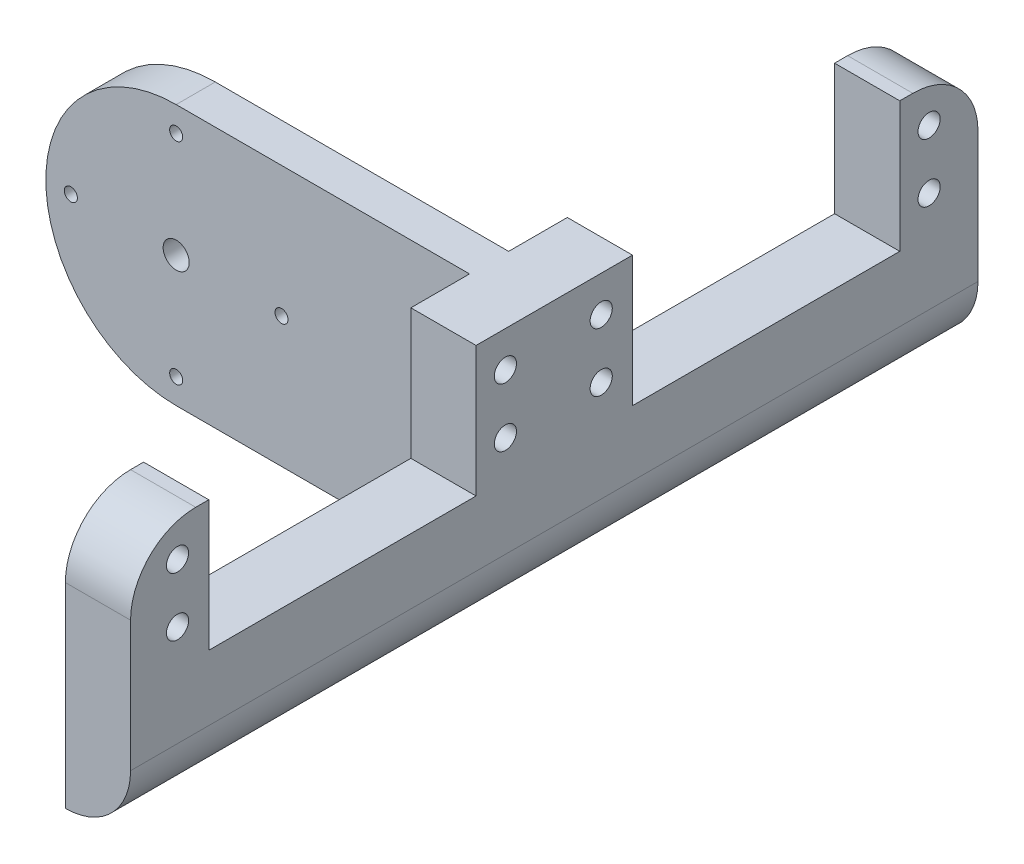
SolidWorks part; units mm, degrees
ref_plane "Front" through (0, 0, 0) normal (0, 0, 1) x (1, 0, 0)
ref_plane "Top" through (0, 0, 0) normal (0, 1, 0) x (1, 0, 0)
ref_plane "Right" through (0, 0, 0) normal (1, 0, 0) x (0, 0, -1)
sketch "스케치1" plane through (0, 0, 0) normal (0, 0, 1) x (1, 0, 0)
  line L0 (0, 20) -> (45, 20)
  line L1 (0, -20) -> (45, -20)
  line L2 (45, 20) -> (45, -20)
  line L3 (0, 16.16) -> (0, 0) construction
  circle A0 centre (0, 0) radius 2
  arc A1 (0, 20) -> (0, -20) centre (0, 0) ccw
  circle A2 centre (0, 16.16) radius 1
  circle A3 centre (16.16, 0) radius 1
  circle A4 centre (0, -16.16) radius 1
  circle A5 centre (-16.16, 0) radius 1
  point P18 (0, 0)
  dimension "D1" = 20
  dimension "D2" = 4
  dimension "D3" = 2
  dimension "D4" = 16.16
  dimension "D5" = 45
extrude "보스-돌출1" add sketch "스케치1" along normal blind 3 and the other way blind 3
sketch "스케치2" plane through (45, 0, 0) normal (1, 0, 0) x (0, 0, -1)
  line L0 (0, 20) -> (0, -20) construction
  line L1 (65, 20) -> (-65, 20)
  line L2 (65, 20) -> (65, -20)
  line L3 (65, -20) -> (-65, -20)
  line L4 (-65, 20) -> (-65, -20)
  dimension "D1" = 130
  dimension "D2" = 40
extrude "보스-돌출2" add sketch "스케치2" along normal blind 10
sketch "스케치3" plane through (55, 0, 0) normal (1, 0, 0) x (0, 0, -1)
  line L0 (0, 20) -> (0, -20) construction
  line L1 (65, 20) -> (-65, 20) construction
  line L2 (-65, -20) -> (65, -20) construction
  line L3 (53, 0) -> (53, 20)
  line L4 (-65, 20) -> (-65, -20) construction
  line L7 (-53, 0) -> (-12, 0)
  line L8 (-53, 0) -> (-53, 20)
  line L9 (-53, 20) -> (-12, 20)
  line L10 (-12, 0) -> (-12, 20)
  line L14 (53, 20) -> (12, 20)
  line L15 (53, 0) -> (12, 0)
  line L16 (12, 0) -> (12, 20)
  dimension "D1" = 12
  dimension "D2" = 12
  dimension "D3" = 20
extrude "컷-돌출1" cut sketch "스케치3" against normal blind 10
fillet "필렛1" radius 10 1 edges at (55, -20, 0)
hole_wizard "M3 여유 구멍1" positions "스케치4" profile "스케치5" hole size "M3" standard "KS" end condition up to next
sketch "스케치4" plane through (55, 0, 0) normal (1, 0, 0) x (0, 0, -1)
  point P0 (-57.8, 14.5)
  point P3 (-57.8, 5.5)
  point P6 (-7.5, 14.5)
  point P9 (-7.5, 5.5)
  point P12 (7.2, 14.5)
  point P15 (7.2, 5.5)
  point P18 (57.5, 14.5)
  point P21 (57.5, 5.5)
sketch "스케치5" plane through (55, 14.5, 57.8) normal (0, 1, 0) x (0, 0, -1)
  line L0 (0, 0) -> (0, 10)
  line L1 (0, 10) -> (1.7, 10)
  line L2 (1.7, 10) -> (1.7, 0)
  line L5 (1.7, 0) -> (0, 0)
  line L11 (0, -6.35) -> (0, 107.95) construction
  dimension "관통 구멍 지름" = 3.4
  dimension "관통 구멍 깊이" = 10
fillet "필렛4" radius 10 2 edges at (50, 20, -65) (50, 20, 65)
